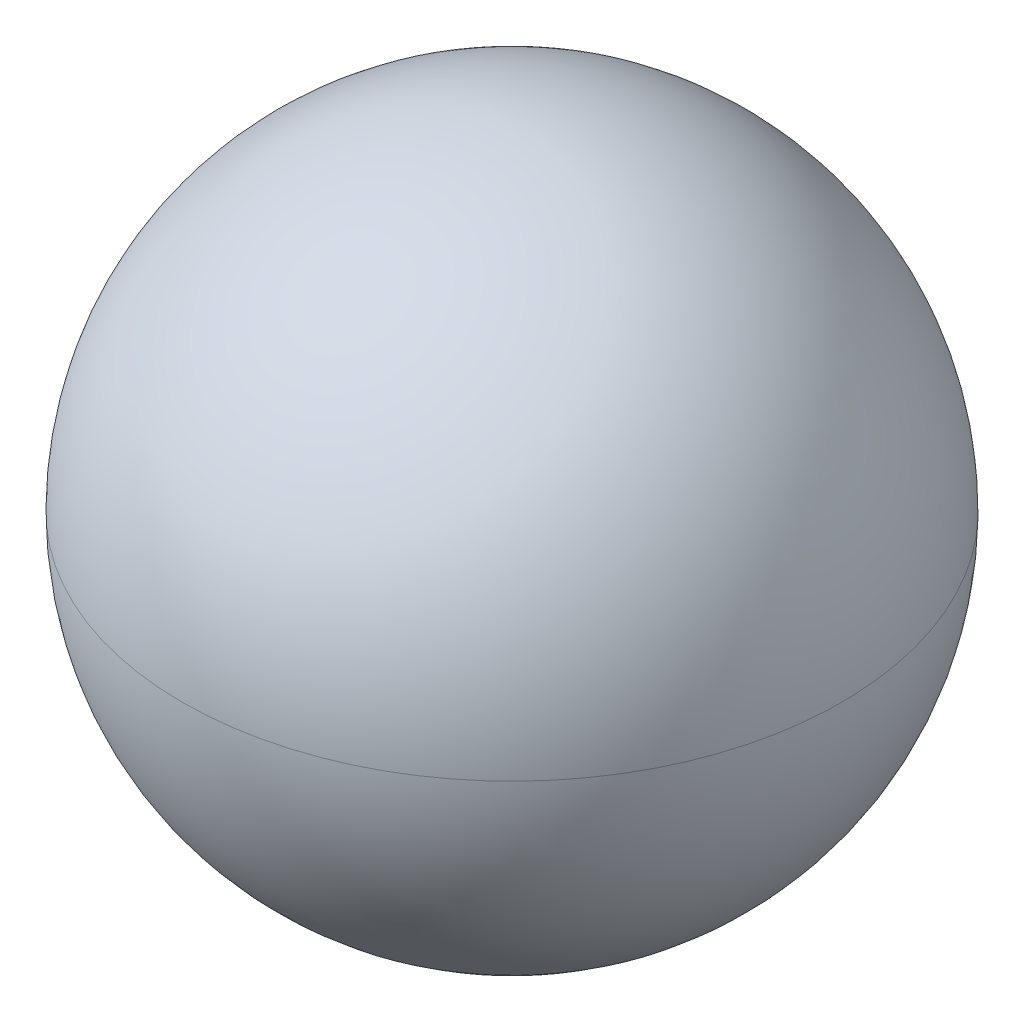
SolidWorks part; units mm, degrees
ref_plane "Front Plane" through (0, 0, 0) normal (0, 0, 1) x (1, 0, 0)
ref_plane "Top Plane" through (0, 0, 0) normal (0, 1, 0) x (1, 0, 0)
ref_plane "Right Plane" through (0, 0, 0) normal (1, 0, 0) x (0, 0, -1)
sketch "Sketch1" plane through (0, 0, 0) normal (0, 1, 0) x (1, 0, 0)
  circle A0 centre (0, 0) radius 3.26
  dimension "D1" = 6.52
extrude "Boss-Extrude1" add sketch "Sketch1" along normal blind 6.5 contours A0
sketch "Sketch2" plane through (0, 0, 0) normal (0, 0, 1) x (1, 0, 0)
  line L0 (0, 6.5) -> (0, 0) construction
  line L1 (3.26, 6.5) -> (-3.26, 6.5) construction
  line L2 (3.26, 3.25) -> (-3.26, 3.25) construction
  line L3 (3.26, 0) -> (3.26, 6.5) construction
  line L4 (-3.26, 6.5) -> (-3.26, 0) construction
  line L8 (0, 6.5) -> (0, 0)
  arc A0 (0, 6.5) -> (3.26, 3.25) centre (0.2715, 3.5123) cw
  arc A1 (0, 0) -> (3.26, 3.25) centre (0.2715, 2.9877) ccw
  dimension "D1" = 3
ref_axis "Axis1" through (0, 6.5, 0) along (0, -1, 0)
fillet "Fillet1" radius 3.26 1 edges at (0, 6.5, 3.26)
fillet "Fillet2" radius 3.26 1 edges at (0, 0, 3.26)
sketch "Sketch3" [suppressed] plane through (0, 0, 0) normal (0, 1, 0) x (1, 0, 0)
  line L0 (0, -3.26) -> (0, 3.26) construction
  line L2 (-3, 0) -> (3, 0) construction
  line L3 (0, 0) -> (3.2715, 0) construction
  line L4 (3.26, 0) -> (-3.26, 0) construction
  circle A0 centre (0, 0) radius 3.26 construction
  point P4 (0, 0)
  point P12 (0, 0)
